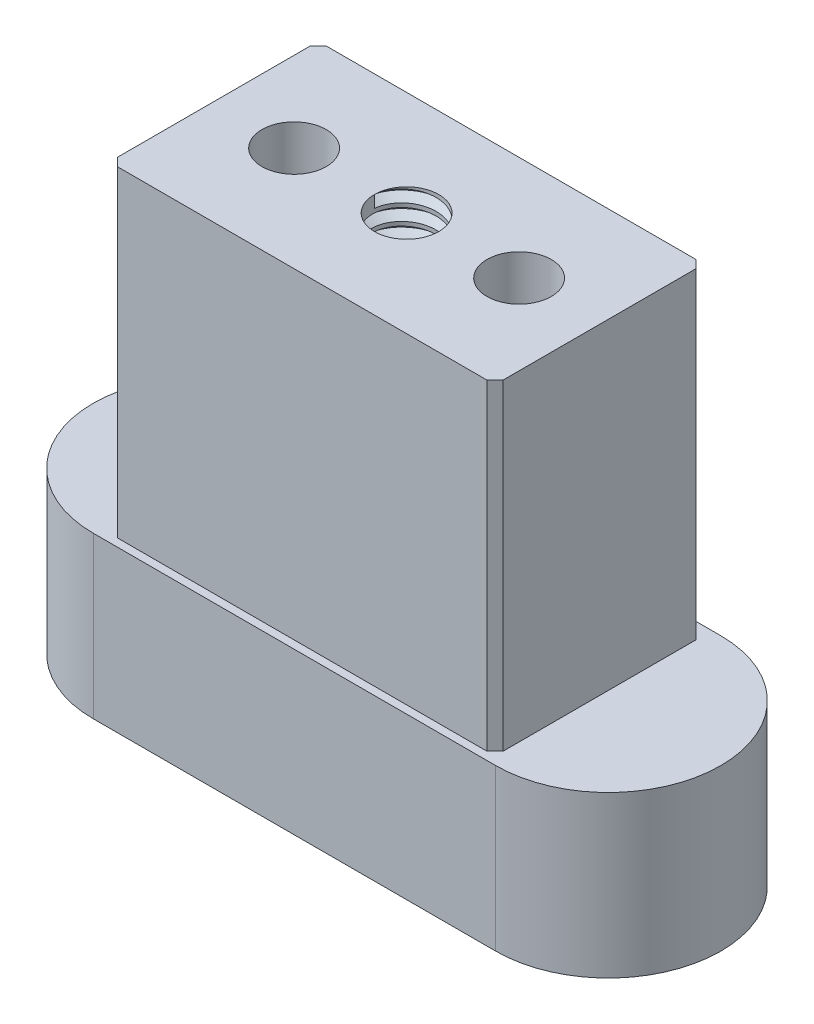
SolidWorks part; units mm, degrees
ref_plane "Front Plane" through (0, 0, 0) normal (0, 0, 1) x (1, 0, 0)
ref_plane "Top Plane" through (0, 0, 0) normal (0, 1, 0) x (1, 0, 0)
ref_plane "Right Plane" through (0, 0, 0) normal (1, 0, 0) x (0, 0, -1)
sketch "Sketch1" plane through (0, 0, 0) normal (0, 1, 0) x (1, 0, 0)
  line L0 (25.0969, 0) -> (25.0484, -14) construction
  line L1 (0, 0) -> (25.0969, 0)
  line L3 (0.0484, -14) -> (25.0484, -14)
  arc A0 (25.0484, -14) -> (25.0969, 0) centre (25.0726, -7) ccw
  arc A1 (0, 0) -> (0.0484, -14) centre (0.0242, -7) ccw
  dimension "D1" = 14
  dimension "D2" = 7
extrude "Boss-Extrude1" add sketch "Sketch1" along normal blind 10
sketch "Sketch3" plane through (0, 10, 0) normal (0, 1, 0) x (1, 0, 0)
  line L1 (24.5242, -13.5) -> (0.5242, -13.5)
  line L2 (24.5242, -13.5) -> (24.5242, -0.5)
  line L3 (24.5242, -0.5) -> (0.5242, -0.5)
  line L4 (0.5242, -13.5) -> (0.5242, -0.5)
  line L13 (0, 0) -> (0.0484, -14) construction
  point P4 (0.5242, -7)
  point P5 (0.0242, -7)
  point P9 (25.0969, 0)
  dimension "D1" = 24
  dimension "D2" = 0.5
sketch "Sketch4" plane through (0, 10, 0) normal (0, 1, 0) x (1, 0, 0)
extrude "Boss-Extrude2" add sketch "Sketch3" along normal blind 20
sketch "Sketch6" plane through (0, 30, 0) normal (0, 1, 0) x (1, 0, 0)
  line L0 (0.5242, -0.5) -> (24.5242, -13.5) construction
  line L1 (24.5242, -0.5) -> (0.5242, -13.5) construction
  circle A0 centre (12.5242, -7) radius 2
  point P10 (0, 0)
  point P11 (0, 0)
  dimension "D1" = 4
hole_wizard "Ø4.0 (4) Diameter Hole1" positions "3DSketch1" profile "Sketch7" hole size "Ø4.0" standard "ANSI Metric"
sketch3d "3DSketch1"
  point P0 (12.5242, 30, 7)
sketch "Sketch7" plane through (12.5242, 30, 7) normal (1, 0, 0) x (0, 0, 1)
  line L0 (0, 0) -> (0, 22)
  line L1 (0, 22) -> (2, 20)
  line L2 (2, 20) -> (2, 0)
  line L5 (2, 0) -> (0, 0)
  line L10 (0, 22) -> (-2, 20) construction
  line L11 (0, -6.35) -> (0, 107.95) construction
  dimension "Hole Dia." = 4
  dimension "Hole Depth" = 20
  dimension "Drill Angle" = 90
thread "Thread1" pitch 1 method cut profile "Thread Profile1" start angle 0, offset 0, length 0, pitch 1, diameter 4
ref_plane "Plane2" through (10.5242, 30, 7) normal (0, 0, 1) x (-1, 0, 0)
sketch "Thread Profile1" plane through (10.5242, 30, 7) normal (0, 0, 1) x (-1, 0, 0)
  line L0 (0, 0) -> (0, 1) construction
  line L1 (0, 0) -> (0.5413, 0.3125)
  line L2 (0.5413, 0.3125) -> (0.5413, 0.4375)
  line L3 (0.5413, 0.4375) -> (0, 0.75)
  line L4 (0.5413, 0.375) -> (0, 0.375) construction
  line L11 (0, 0) -> (0, 0.75)
  point P2 (0, 0)
  dimension "Pitch" = 1
  dimension "Profile_Angle" = 60
  dimension "Profile_Land" = 0.125
  dimension "Profile_Height" = 0.5413
chamfer "Chamfer1" distance 0.5 angle 45 4 edges at (24.5242, 20, 0.5) (24.5242, 20, 13.5) (0.5242, 20, 13.5) (0.5242, 20, 0.5)
sketch "Sketch19" plane through (0, 30, 0) normal (0, 1, 0) x (1, 0, 0)
  circle A0 centre (5.5242, -7) radius 2
  circle A1 centre (19.5242, -7) radius 2
extrude "Cut-Extrude2" cut sketch "Sketch19" against normal blind 30 contours A0
sketch "Sketch20" plane through (0, 30, 0) normal (0, 1, 0) x (1, 0, 0)
  circle A0 centre (19.5242, -7) radius 2
extrude "Cut-Extrude3" cut sketch "Sketch20" against normal blind 30
